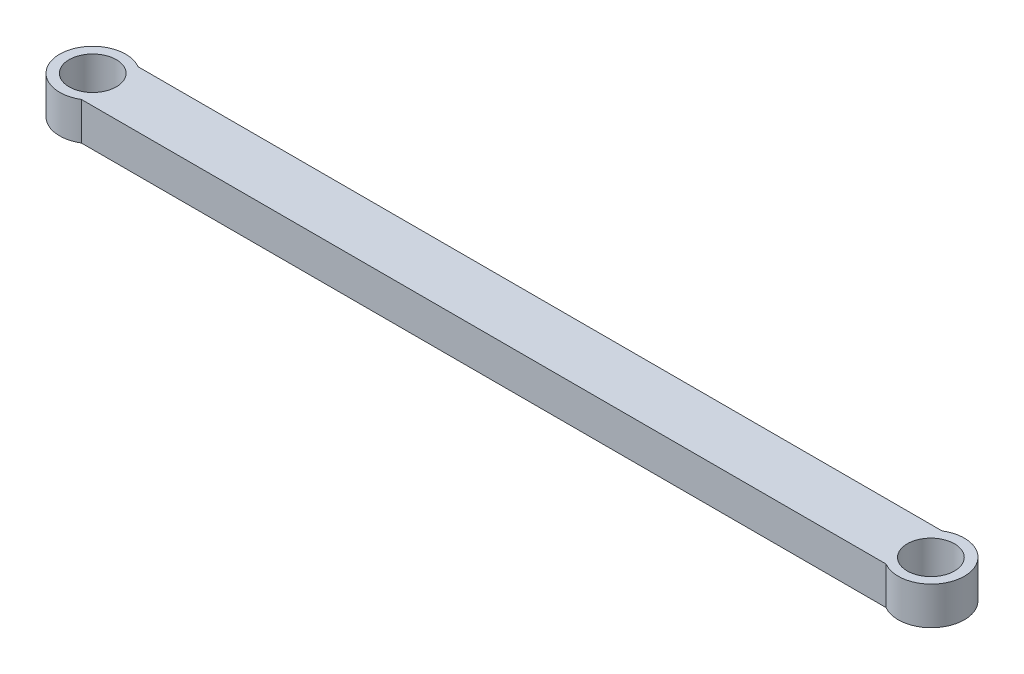
SolidWorks part; units mm, degrees
ref_plane "Front Plane" through (0, 0, 0) normal (0, 0, 1) x (1, 0, 0)
ref_plane "Top Plane" through (0, 0, 0) normal (0, 1, 0) x (1, 0, 0)
ref_plane "Right Plane" through (0, 0, 0) normal (1, 0, 0) x (0, 0, -1)
sketch "Sketch2" plane through (0, 0, 0) normal (0, 1, 0) x (1, 0, 0)
  line L0 (0, 1.75) -> (0, 1.25)
  line L1 (0, -1.25) -> (0, -1.75)
  line L2 (0, 1.5) -> (44.3835, 1.5)
  line L3 (0, -1.5) -> (44.3835, -1.5)
  line L4 (44.3835, 1.7605) -> (44.3835, 1.2395)
  line L5 (44.3835, -1.2605) -> (44.3835, -1.7395)
  circle A0 centre (0, 0) radius 1.75
  circle A1 centre (0, 0) radius 1.25
  circle A2 centre (44.3835, 0.0105) radius 1.75
  circle A3 centre (44.3835, -0.0105) radius 1.25
  point P22 (44.3835, 1.5)
  dimension "D1" = 3.5
  dimension "D3" = 3.5
  dimension "D2" = 0.5
extrude "Boss-Extrude1" add sketch "Sketch2" along normal blind 2 contours A2 L2 A0 L3 | A1 L1 L3 A0 L2 L0 | A1 L0 A0 L1 | A3 L5 A2 L4 | A3 L4 L2 A2 L3 L5 | L2 A0 L0 | L1 A0 L3 | L4 A2 L2 | L3 A2 L5 region at (0.3415, 0, -1.6006) region at (-0.0391, 0, -1.625) region at (0.4507, 0, -1.4653) region at (0.3415, 0, 1.6006) region at (22.1918, 0, 0.0002) region at (44.0353, 0, -1.6049) region at (43.9242, 0, -1.4653) region at (44.0489, 0, 1.5964) region at (44.4226, 0, -1.6303)
sketch "Sketch3" plane through (0, 0, 0) normal (0, -1, 0) x (1, 0, 0)
  circle A0 centre (0, 0) radius 1.25
  circle A1 centre (44.3835, 0.0105) radius 1.25
  dimension "D1" = 2.5
  dimension "D2" = 2.5
